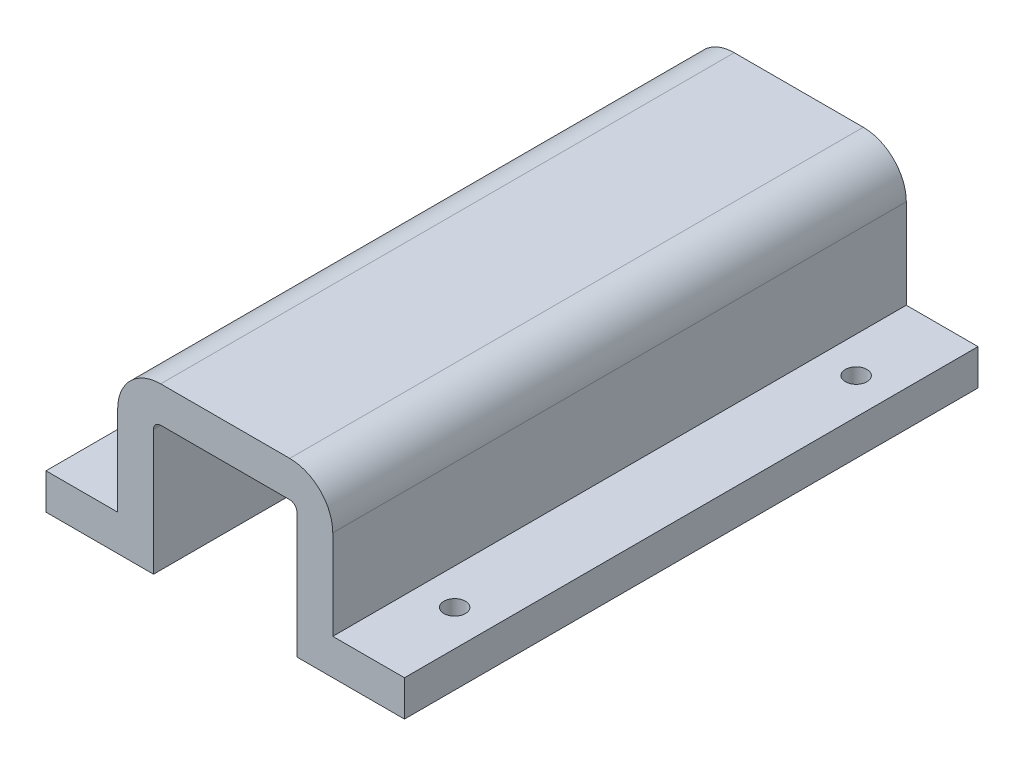
SolidWorks part; units mm, degrees
material "20% infill ABS"
ref_plane "Front" through (0, 0, 0) normal (0, 0, 1) x (1, 0, 0)
ref_plane "Top" through (0, 0, 0) normal (0, 1, 0) x (1, 0, 0)
ref_plane "Right" through (0, 0, 0) normal (1, 0, 0) x (0, 0, -1)
sketch "Sketch1" plane through (0, 0, 0) normal (0, 0, 1) x (1, 0, 0)
  line L0 (9, 15) -> (-9, 15)
  line L1 (-15, 9) -> (-15, -3.5)
  line L3 (15, -3.5) -> (15, 9)
  line L4 (10, -9) -> (10, 9)
  line L5 (9, 10) -> (-9, 10)
  line L6 (-10, 9) -> (-10, -9)
  line L7 (-9, -10) -> (9, -10)
  line L9 (9, 10) -> (-9, 10)
  line L11 (-9, -10) -> (9, -10) construction
  line L12 (-9, -15) -> (9, -15) construction
  line L14 (-15, -3.5) -> (-25, -3.5)
  line L15 (-25, -3.5) -> (-25, -8.5)
  line L16 (-25, -8.5) -> (-10, -8.5)
  line L17 (25, -8.5) -> (25, -3.5)
  line L18 (25, -3.5) -> (15, -3.5)
  line L20 (15, -9) -> (15, 9) construction
  line L21 (-15, 9) -> (-15, -9) construction
  line L22 (10, -9) -> (10, -8.5) construction
  line L23 (-10, -9) -> (-10, -8.5) construction
  line L24 (10, -8.5) -> (25, -8.5)
  line L25 (10, 9) -> (10, -8.5)
  line L26 (-10, 9) -> (-10, -8.5)
  line L29 (-10, 9) -> (-10, -9) construction
  line L30 (10, -9) -> (10, 9) construction
  arc A0 (-9, 15) -> (-15, 9) centre (-9, 9) ccw
  arc A3 (15, 9) -> (9, 15) centre (9, 9) ccw
  arc A4 (9, -10) -> (10, -9) centre (9, -9) ccw
  arc A5 (10, 9) -> (9, 10) centre (9, 9) ccw
  arc A6 (-9, 10) -> (-10, 9) centre (-9, 9) ccw
  arc A7 (-10, -9) -> (-9, -10) centre (-9, -9) ccw
  arc A8 (9, -10) -> (10, -9) centre (9, -9) ccw construction
  arc A9 (10, 9) -> (9, 10) centre (9, 9) ccw
  arc A10 (-9, 10) -> (-10, 9) centre (-9, 9) ccw
  arc A11 (-10, -9) -> (-9, -10) centre (-9, -9) ccw construction
  arc A12 (-15, -9) -> (-9, -15) centre (-9, -9) ccw construction
  arc A13 (9, -15) -> (15, -9) centre (9, -9) ccw construction
  point P29 (10, -8.5)
  dimension "D3" = 10
  dimension "D4" = 10
  dimension "D5" = 5
  dimension "D6" = 1.5
  dimension "D1" = 0
  dimension "D2" = 5
extrude "Boss-Extrude1" add sketch "Sketch1" along normal blind 80
hole_wizard "Ø3.0mm Dowel Hole1" positions "Sketch2" profile "Sketch3" hole size "Ø3.0" standard "ANSI Metric" end condition through all
sketch "Sketch2" plane through (0, -3.5, 0) normal (0, 1, 0) x (1, 0, 0)
  line L0 (-15, 0) -> (-25, 0) construction
  line L2 (-15, -80) -> (-25, -80) construction
  line L4 (25, -80) -> (15, -80) construction
  line L5 (25, 0) -> (15, 0) construction
  line L6 (15, -80) -> (15, 0) construction
  line L7 (-15, -80) -> (-15, 0) construction
  point P0 (-20, -12)
  point P5 (-20, -68)
  point P7 (20, -12)
  point P9 (20, -68)
  dimension "D1" = 12
  dimension "D2" = 5
  dimension "D3" = 5
  dimension "D4" = 12
  dimension "D5" = 5
  dimension "D6" = 12
  dimension "D7" = 5
  dimension "D8" = 12
sketch "Sketch3" plane through (-20, -3.5, 12) normal (1, 0, 0) x (0, 0, 1)
  line L0 (0, 0) -> (0, 5)
  line L1 (0, 5) -> (1.5, 5)
  line L2 (1.5, 5) -> (1.5, 0)
  line L5 (1.5, 0) -> (0, 0)
  line L11 (0, -6.35) -> (0, 107.95) construction
  dimension "Thru Hole Dia." = 3
  dimension "Thru Hole Depth" = 5
